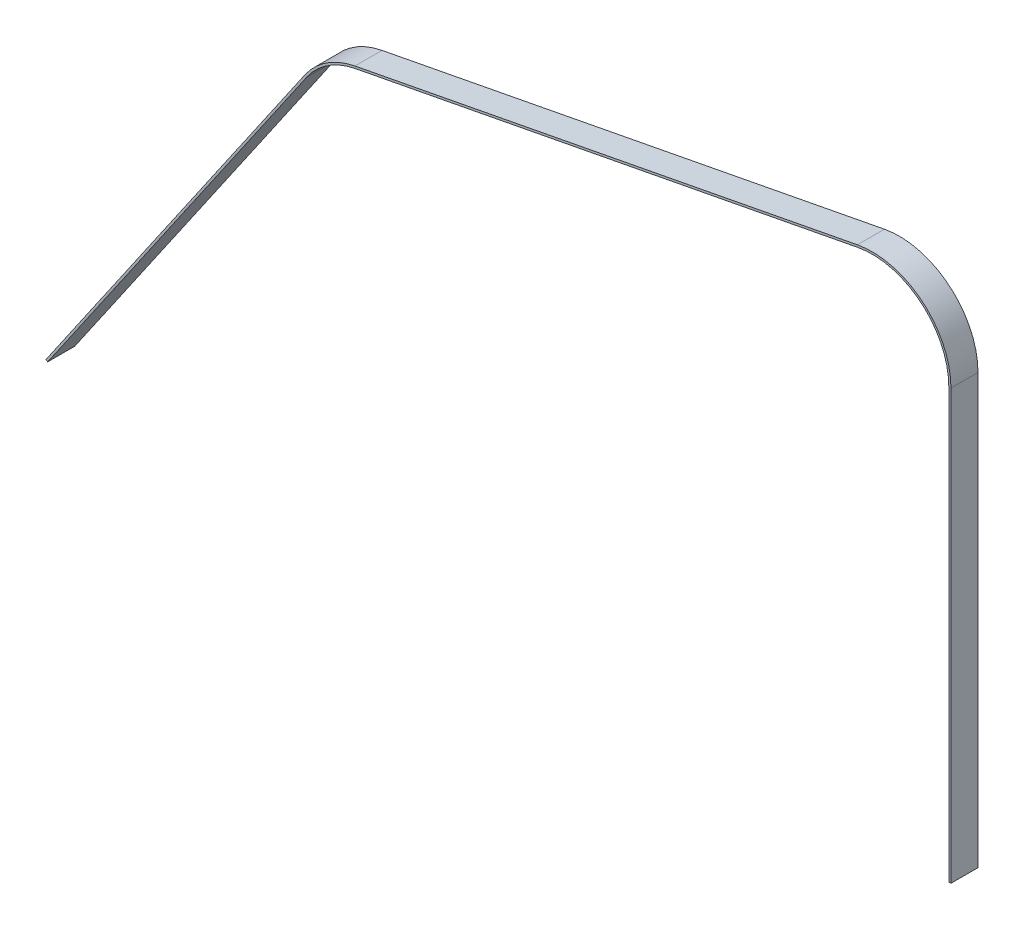
SolidWorks part; units mm, degrees
ref_plane "Front Plane" through (0, 0, 0) normal (0, 0, 1) x (1, 0, 0)
ref_plane "Top Plane" through (0, 0, 0) normal (0, 1, 0) x (1, 0, 0)
ref_plane "Right Plane" through (0, 0, 0) normal (1, 0, 0) x (0, 0, -1)
sketch "Sketch1" plane through (0, 0, 0) normal (0, 0, 1) x (1, 0, 0)
  line L0 (-6.9632, 36.3054) -> (229.0168, 81.5651)
  line L1 (0, 0) -> (17.6005, 3.3757) construction
  line L2 (229.0168, 81.5651) -> (236.3467, 43.3474) construction
  line L3 (-30.4453, 20.968) -> (-152.0404, -155.5871)
  line L4 (-152.0404, -155.5871) -> (-151.2169, -156.1543)
  line L5 (-151.2169, -156.1543) -> (-29.6217, 20.4008)
  line L6 (-6.9632, 36.3054) -> (0, 0) construction
  line L7 (-6.7748, 35.3233) -> (229.2052, 80.583)
  line L8 (272.9471, 45.2596) -> (272.9471, -156.1543)
  line L9 (272.9471, -156.1543) -> (271.9471, -156.1543)
  line L10 (271.9471, -156.1543) -> (271.9471, 45.2596)
  arc A0 (-30.4453, 20.968) -> (-6.9632, 36.3054) centre (0, 0) cw
  arc A1 (229.0168, 81.5651) -> (272.9471, 45.2596) centre (235.98, 45.2596) cw
  arc A2 (-29.6217, 20.4008) -> (-6.7748, 35.3233) centre (0, 0) cw
  arc A3 (271.9471, 45.2596) -> (229.2052, 80.583) centre (235.98, 45.2596) ccw
  point P18 (0, 0)
  dimension "D5" = 36.9672
  dimension "D1" = 1
  dimension "D2" = 214.376
  dimension "D3" = 1
  dimension "D4" = 423.164
  dimension "D6" = 201.4139
extrude "Boss-Extrude1" add sketch "Sketch1" along normal blind 12.7 contours A3 L10 L9 L8 A1 L0 A0 L3 L4 L5 A2 L7 region at (111.1186, 58.4567, 0)
